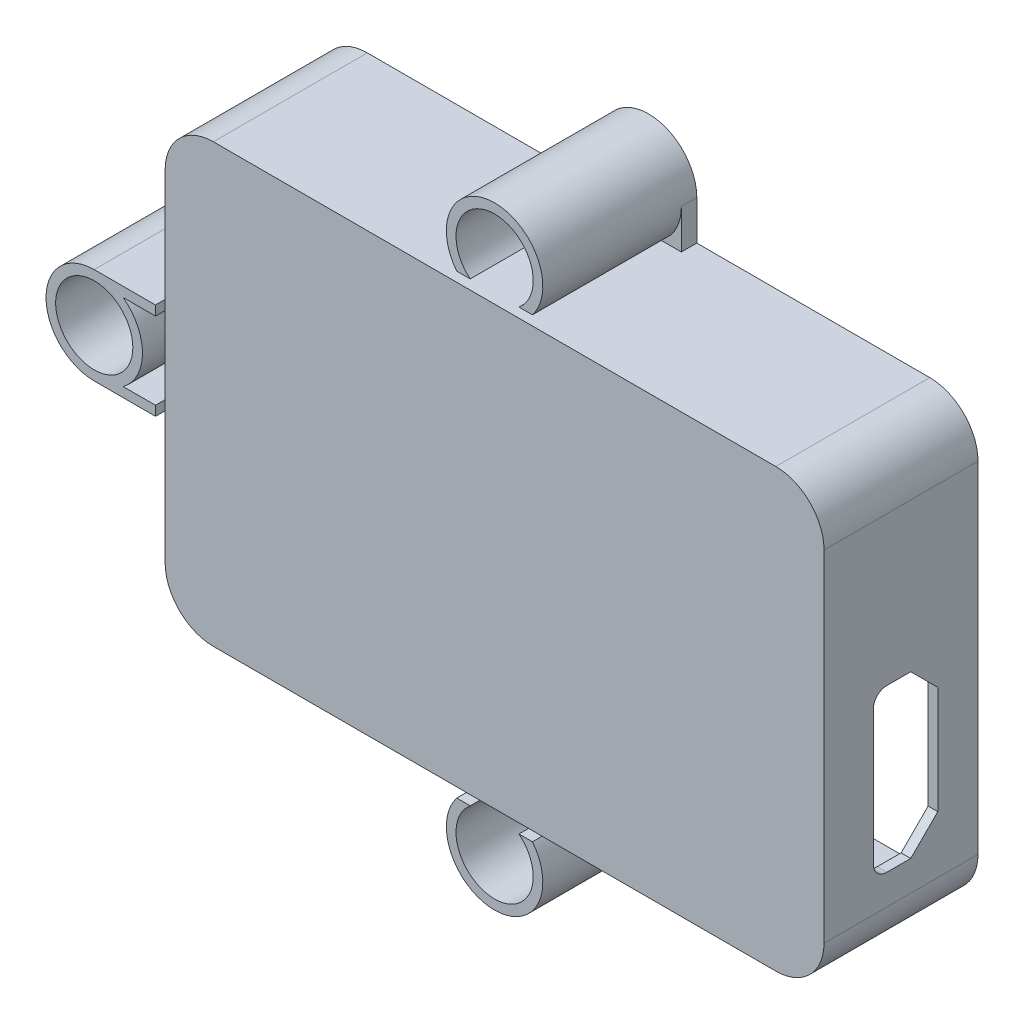
SolidWorks part; units mm, degrees
ref_plane "Front Plane" through (0, 0, 0) normal (0, 0, 1) x (1, 0, 0)
ref_plane "Top Plane" through (0, 0, 0) normal (0, 1, 0) x (1, 0, 0)
ref_plane "Right Plane" through (0, 0, 0) normal (1, 0, 0) x (0, 0, -1)
sketch "Sketch1" plane through (0, 0, 0) normal (0, 0, 1) x (1, 0, 0)
  line L1 (-14.575, -11.325) -> (14.575, -11.325)
  line L2 (-17.075, -8.825) -> (-17.075, 8.825)
  line L3 (-14.575, 11.325) -> (14.575, 11.325)
  line L4 (17.075, -8.825) -> (17.075, 8.825)
  line L5 (-17.075, -11.325) -> (17.075, 11.325) construction
  line L6 (-17.075, 11.325) -> (17.075, -11.325) construction
  line L8 (-16.575, 10.825) -> (-17.075, 10.825) construction
  line L9 (14.575, -10.825) -> (-14.575, -10.825)
  line L10 (16.575, -8.825) -> (16.575, 8.825)
  line L11 (14.575, 10.825) -> (-14.575, 10.825)
  line L12 (-16.575, -8.825) -> (-16.575, 8.825)
  line L13 (16.575, -10.825) -> (-16.575, 10.825) construction
  line L14 (16.575, 10.825) -> (-16.575, -10.825) construction
  line L15 (-16.575, 10.825) -> (-16.575, 11.325) construction
  line L16 (-16.375, 9.825) -> (-16.375, -9.825) construction
  line L17 (16.375, 9.825) -> (-16.375, 9.825) construction
  line L18 (-2.5, 13.375) -> (-2.5, 11.325)
  line L19 (2.5, 13.375) -> (2.5, 11.325)
  line L20 (-2.5, -13.375) -> (-2.5, -11.325)
  line L21 (2.5, -13.375) -> (2.5, -11.325)
  line L22 (-20.75, 2.5) -> (-17.075, 2.5)
  line L23 (-20.75, -2.5) -> (-17.075, -2.5)
  arc A0 (-14.575, -10.825) -> (-16.575, -8.825) centre (-14.575, -8.825) cw
  arc A1 (-2.4744, -13.0179) -> (2.4744, -13.0179) centre (0, -13.375) ccw construction
  arc A2 (14.575, -10.825) -> (16.575, -8.825) centre (14.575, -8.825) ccw
  arc A3 (16.575, 8.825) -> (14.575, 10.825) centre (14.575, 8.825) ccw
  arc A4 (-20.3929, 2.4744) -> (-20.3929, -2.4744) centre (-20.75, 0) ccw construction
  arc A5 (-14.575, 10.825) -> (-16.575, 8.825) centre (-14.575, 8.825) ccw
  arc A6 (-14.575, -11.325) -> (-17.075, -8.825) centre (-14.575, -8.825) cw
  arc A7 (14.575, -11.325) -> (17.075, -8.825) centre (14.575, -8.825) ccw
  arc A8 (2.4744, 13.0179) -> (-2.4744, 13.0179) centre (0, 13.375) ccw construction
  circle A9 centre (-20.75, 0) radius 1.25
  arc A10 (-2.4744, -13.0179) -> (2.4744, -13.0179) centre (0, -13.375) ccw
  circle A11 centre (0, 13.375) radius 1.25
  circle A12 centre (0, -13.375) radius 1.25
  arc A13 (-20.3929, 2.4744) -> (-20.3929, -2.4744) centre (-20.75, 0) ccw
  arc A14 (14.575, 11.325) -> (17.075, 8.825) centre (14.575, 8.825) cw
  arc A15 (-17.075, 8.825) -> (-14.575, 11.325) centre (-14.575, 8.825) cw
  arc A17 (2.4744, 13.0179) -> (-2.4744, 13.0179) centre (0, 13.375) ccw
  point P0 (0, 0)
  point P31 (0, 0)
  dimension "D4" = 2.5
  dimension "D5" = 2
  dimension "D6" = 2.5
  dimension "D1" = 0.5
  dimension "D2" = 0.2
  dimension "D3" = 1
extrude "Boss-Extrude1" add sketch "Sketch1" along normal offset from surface (7.48 mm away) 2.5 contours A13 L2 | L1 L4 L3 L2 L9 L12 L11 L10 | A17 L3 | A10 L1 region at (-16.053, -10.303, 0) region at (0, -11.3926, 0) region at (-18.9125, -2.4205, 0) region at (-2.4324, 12.35, 0) offset beyond the face yes
sketch "Sketch2" plane through (0, 0, 7.48) normal (0, 0, 1) x (1, 0, 0)
  line L0 (-2.5, 11.325) -> (2.5, 11.325)
  line L1 (-17.075, 2.5) -> (-17.075, -2.5)
  line L2 (-2.5, -11.325) -> (2.5, -11.325)
  line L13 (-17.075, 2.5) -> (-20.75, 2.5)
  line L14 (-20.75, -2.5) -> (-17.075, -2.5)
  line L15 (-17.075, -2.5) -> (-17.075, -8.825)
  line L16 (-14.575, -11.325) -> (-2.5, -11.325)
  line L17 (-2.5, -11.325) -> (-2.5, -13.375)
  line L18 (2.5, -13.375) -> (2.5, -11.325)
  line L19 (2.5, -11.325) -> (14.575, -11.325)
  line L20 (17.075, -8.825) -> (17.075, 8.825)
  line L21 (14.575, 11.325) -> (2.5, 11.325)
  line L22 (2.5, 11.325) -> (2.5, 13.375)
  line L23 (-2.5, 13.375) -> (-2.5, 11.325)
  line L24 (-2.5, 11.325) -> (-14.575, 11.325)
  line L25 (-17.075, 8.825) -> (-17.075, 2.5)
  line L26 (-17.075, 2.5) -> (-20.75, 2.5)
  line L27 (-20.75, -2.5) -> (-17.075, -2.5)
  line L28 (-17.075, -2.5) -> (-17.075, -8.825)
  line L29 (-14.575, -11.325) -> (-2.5, -11.325)
  line L30 (-2.5, -11.325) -> (-2.5, -13.375)
  line L31 (2.5, -13.375) -> (2.5, -11.325)
  line L32 (2.5, -11.325) -> (14.575, -11.325)
  line L33 (17.075, -8.825) -> (17.075, 8.825)
  line L34 (14.575, 11.325) -> (2.5, 11.325)
  line L35 (2.5, 11.325) -> (2.5, 13.375)
  line L36 (-2.5, 13.375) -> (-2.5, 11.325)
  line L37 (-2.5, 11.325) -> (-14.575, 11.325)
  line L38 (-17.075, 8.825) -> (-17.075, 2.5)
  arc A7 (-20.75, 2.5) -> (-20.75, -2.5) centre (-20.75, 0) ccw
  arc A8 (-17.075, -8.825) -> (-14.575, -11.325) centre (-14.575, -8.825) ccw
  arc A9 (-2.5, -13.375) -> (2.5, -13.375) centre (0, -13.375) ccw
  arc A10 (14.575, -11.325) -> (17.075, -8.825) centre (14.575, -8.825) ccw
  arc A11 (17.075, 8.825) -> (14.575, 11.325) centre (14.575, 8.825) ccw
  arc A12 (2.5, 13.375) -> (-2.5, 13.375) centre (0, 13.375) ccw
  arc A13 (-14.575, 11.325) -> (-17.075, 8.825) centre (-14.575, 8.825) ccw
  arc A14 (-20.75, 2.5) -> (-20.75, -2.5) centre (-20.75, 0) ccw
  arc A15 (-17.075, -8.825) -> (-14.575, -11.325) centre (-14.575, -8.825) ccw
  arc A16 (-2.5, -13.375) -> (2.5, -13.375) centre (0, -13.375) ccw
  arc A17 (14.575, -11.325) -> (17.075, -8.825) centre (14.575, -8.825) ccw
  arc A18 (17.075, 8.825) -> (14.575, 11.325) centre (14.575, 8.825) ccw
  arc A19 (2.5, 13.375) -> (-2.5, 13.375) centre (0, 13.375) ccw
  arc A20 (-14.575, 11.325) -> (-17.075, 8.825) centre (-14.575, 8.825) ccw
  dimension "D1" = 0
extrude "Cut-Extrude1" cut sketch "Sketch2" against normal offset from surface (6.68 mm away) 0.8 contours L0 | L1 | L2 region at (0, 13.3705, 7.48) region at (-19.9219, 0, 7.48) region at (0, -13.3705, 7.48) up to face at (-3.9075, 0, 0)
sketch "Sketch3" plane through (17.075, 0, 0) normal (1, 0, 0) x (0, 0, -1)
  line L0 (-3.98, -7.065) -> (-4.18, -7.065) construction
  line L1 (-5.425, -7.265) -> (-2.085, -7.265)
  line L2 (-5.425, -7.265) -> (-5.425, 1.115)
  line L3 (-5.425, 1.115) -> (-2.085, 1.115)
  line L4 (-2.085, -7.265) -> (-2.085, 1.115)
  line L5 (-5.225, -6.075) -> (-5.425, -6.075) construction
  line L6 (-4.18, -7.065) -> (-4.18, -7.265) construction
  line L7 (-4.18, 0.915) -> (-4.18, 1.115) construction
  line L8 (-2.285, -5.375) -> (-2.085, -5.375) construction
  dimension "D1" = 0.2
extrude "Cut-Extrude2" cut sketch "Sketch3" against normal up to next
chamfer "Chamfer1" distance 1.4 angle 45 2 edges at (16.825, 1.115, 2.085) (16.825, -7.265, 2.085)
fillet "Fillet1" radius 0.7 2 edges at (16.825, 1.115, 5.425) (16.825, -7.265, 5.425)
sketch "Sketch4" plane through (0, 0, 7.48) normal (0, 0, 1) x (1, 0, 0)
  line L4 (-17.075, 8.825) -> (-17.075, -8.825)
  line L5 (-14.575, -11.325) -> (14.575, -11.325)
  line L6 (17.075, -8.825) -> (17.075, 8.825)
  line L7 (14.575, 11.325) -> (-14.575, 11.325)
  line L8 (-17.075, 8.825) -> (-17.075, -8.825)
  line L9 (-14.575, -11.325) -> (14.575, -11.325)
  line L10 (17.075, -8.825) -> (17.075, 8.825)
  line L11 (14.575, 11.325) -> (-14.575, 11.325)
  arc A4 (-17.075, -8.825) -> (-14.575, -11.325) centre (-14.575, -8.825) ccw
  arc A5 (14.575, -11.325) -> (17.075, -8.825) centre (14.575, -8.825) ccw
  arc A6 (17.075, 8.825) -> (14.575, 11.325) centre (14.575, 8.825) ccw
  arc A7 (-14.575, 11.325) -> (-17.075, 8.825) centre (-14.575, 8.825) ccw
  arc A8 (-17.075, -8.825) -> (-14.575, -11.325) centre (-14.575, -8.825) ccw
  arc A9 (14.575, -11.325) -> (17.075, -8.825) centre (14.575, -8.825) ccw
  arc A10 (17.075, 8.825) -> (14.575, 11.325) centre (14.575, 8.825) ccw
  arc A11 (-14.575, 11.325) -> (-17.075, 8.825) centre (-14.575, 8.825) ccw
  dimension "D1" = 0
extrude "Boss-Extrude2" add sketch "Sketch4" along normal blind 0.5
sketch "Sketch6" plane through (0, 0, 7.48) normal (0, 0, -1) x (-1, 0, 0)
  line L1 (-14.575, -10.825) -> (-16.575, -10.825)
  line L2 (-14.575, -10.825) -> (-14.575, -9.325)
  line L3 (-14.575, -9.325) -> (-16.575, -9.325)
  line L4 (16.575, -8.825) -> (16.575, 8.825)
  line L5 (14.575, 10.825) -> (-14.575, 10.825)
  line L6 (-16.575, 8.825) -> (-16.575, -8.825)
  line L7 (-14.575, -10.825) -> (14.575, -10.825)
  line L8 (16.575, -8.825) -> (16.575, 8.825)
  line L9 (14.575, 10.825) -> (-14.575, 10.825)
  line L10 (-16.575, 8.825) -> (-16.575, -8.825)
  line L11 (-14.575, -10.825) -> (14.575, -10.825)
  line L12 (-16.575, -10.825) -> (-16.575, -9.325)
  line L13 (-16.575, 1.915) -> (-14.575, 1.915)
  line L14 (-16.575, 1.915) -> (-16.575, 3.415)
  line L15 (-16.575, 3.415) -> (-14.575, 3.415)
  line L16 (-14.575, 1.915) -> (-14.575, 3.415)
  line L17 (-14.575, 10.825) -> (-16.575, 10.825)
  line L18 (-14.575, 10.825) -> (-14.575, 9.325)
  line L19 (-14.575, 9.325) -> (-16.575, 9.325)
  line L20 (-16.575, 10.825) -> (-16.575, 9.325)
  line L21 (16.575, 10.825) -> (14.575, 10.825)
  line L22 (16.575, 10.825) -> (16.575, 9.325)
  line L23 (16.575, 9.325) -> (14.575, 9.325)
  line L24 (14.575, 10.825) -> (14.575, 9.325)
  line L25 (10.575, -10.825) -> (7.575, -10.825)
  line L26 (10.575, -10.825) -> (10.575, -9.325)
  line L27 (10.575, -9.325) -> (7.575, -9.325)
  line L28 (7.575, -10.825) -> (7.575, -9.325)
  arc A4 (14.575, -10.825) -> (16.575, -8.825) centre (14.575, -8.825) ccw
  arc A5 (16.575, 8.825) -> (14.575, 10.825) centre (14.575, 8.825) ccw
  arc A6 (-14.575, 10.825) -> (-16.575, 8.825) centre (-14.575, 8.825) ccw
  arc A7 (-16.575, -8.825) -> (-14.575, -10.825) centre (-14.575, -8.825) ccw
  arc A8 (14.575, -10.825) -> (16.575, -8.825) centre (14.575, -8.825) ccw
  arc A9 (16.575, 8.825) -> (14.575, 10.825) centre (14.575, 8.825) ccw
  arc A10 (-14.575, 10.825) -> (-16.575, 8.825) centre (-14.575, 8.825) ccw
  arc A11 (-16.575, -8.825) -> (-14.575, -10.825) centre (-14.575, -8.825) ccw
  dimension "D2" = 1.5
  dimension "D3" = 1.5
  dimension "D5" = 3
  dimension "D6" = 6
  dimension "D1" = 0
extrude "Boss-Extrude4" add sketch "Sketch6" along normal offset from surface (4.98 mm away) 2.5 contours L28 L11 L26 L27 | L2 L3 | L13 L16 L15 L10 | L19 L18 | L24 L23 region at (15.3591, -9.9498, 7.48) region at (-9.075, -10.075, 7.48) region at (15.575, 2.665, 7.48) region at (-15.3591, 9.9498, 7.48) region at (15.3591, 9.9498, 7.48) up to face at (-3.9075, 0, 0)
sketch "Sketch7" plane through (0, 0, 7.48) normal (0, 0, -1) x (-1, 0, 0)
  line L0 (16.575, -8.825) -> (16.575, 8.825) construction
  line L1 (16.575, 4.185) -> (10.455, 4.185)
  line L2 (16.575, 4.185) -> (16.575, 6.185)
  line L3 (16.575, 6.185) -> (10.455, 6.185)
  line L4 (10.455, 4.185) -> (10.455, 6.185)
  line L5 (16.875, 3.985) -> (10.655, 3.985) construction
  line L6 (10.655, 3.985) -> (10.655, 4.185) construction
  line L7 (10.455, 2.5) -> (5.855, 2.5)
  line L8 (10.455, 2.5) -> (10.455, 4.5)
  line L9 (10.455, 4.5) -> (5.855, 4.5)
  line L10 (5.855, 2.5) -> (5.855, 4.5)
  line L11 (10.655, 3.985) -> (10.455, 3.985) construction
  line L12 (10.455, 2.5) -> (10.455, 2.3) construction
  line L13 (10.655, 2.3) -> (6.055, 2.3) construction
  line L14 (6.055, 2.3) -> (5.855, 2.3) construction
  line L15 (5.855, 3.8) -> (3.855, 3.8)
  line L16 (5.855, 3.8) -> (5.855, 1.8)
  line L17 (5.855, 1.8) -> (3.855, 1.8)
  line L18 (3.855, 3.8) -> (3.855, 1.8)
  line L19 (-5.1149, 0) -> (3.3954, 0) construction
  line L20 (16.575, -4.185) -> (16.575, -6.185)
  line L21 (16.575, -6.185) -> (10.455, -6.185)
  line L22 (16.575, -4.185) -> (10.455, -4.185)
  line L23 (10.455, -4.185) -> (10.455, -6.185)
  line L24 (10.455, -2.5) -> (10.455, -4.5)
  line L25 (10.455, -4.5) -> (5.855, -4.5)
  line L26 (5.855, -2.5) -> (5.855, -4.5)
  line L27 (10.455, -2.5) -> (5.855, -2.5)
  line L28 (5.855, -3.8) -> (5.855, -1.8)
  line L29 (5.855, -3.8) -> (3.855, -3.8)
  line L30 (3.855, -3.8) -> (3.855, -1.8)
  line L31 (5.855, -1.8) -> (3.855, -1.8)
  line M32 (16.575, -8.825) -> (16.575, 8.825)
  dimension "D1" = 0.2
  dimension "D2" = 2
  dimension "D3" = 0.5
extrude "Boss-Extrude5" add sketch "Sketch7" along normal blind 2.5 contours L4 L1 L3 M32 | L10 L7 L8 L4 L9 | L15 L18 L17 L16 L10 | L28 L31 L30 L29 L26 | L24 L27 L26 L25 L23 | L22 L23 L21 M32 region at (-13.515, 5.185, 7.48) region at (-13.515, -5.185, 7.48) region at (-8.155, 3.5, 7.48) region at (-8.155, -3.5, 7.48) region at (-4.855, 2.8, 7.48) region at (-4.855, -2.8, 7.48)
sketch "Sketch8" plane through (-17.075, 0, 0) normal (-1, 0, 0) x (0, 0, 1)
  line L0 (7.48, -4.185) -> (7.48, 4.185) construction
  line L1 (7.48, -4.185) -> (4.88, -4.185)
  line L2 (7.48, -4.185) -> (7.48, 4.185)
  line L3 (7.48, 4.185) -> (4.88, 4.185)
  line L4 (4.88, -4.185) -> (4.88, 4.185)
  line L5 (4.98, 4.185) -> (7.48, 4.185) construction
  line L6 (4.98, -4.185) -> (7.48, -4.185) construction
  dimension "D1" = 2.6
extrude "Cut-Extrude3" cut sketch "Sketch8" against normal up to next
sketch "Sketch5" plane through (0, 0, 0.8) normal (0, 0, 1) x (1, 0, 0)
  line L0 (2.5, -13.375) -> (2.5, -11.325) construction
  line L1 (2.5, -11.325) -> (-2.5, -11.325) construction
  line L2 (-2.5, -11.325) -> (-2.5, -13.375) construction
  line L3 (-2.5, 13.375) -> (-2.5, 11.325) construction
  line L4 (-2.5, 11.325) -> (2.5, 11.325) construction
  line L5 (2.5, 11.325) -> (2.5, 13.375) construction
  line L6 (-20.75, -2.5) -> (-17.075, -2.5) construction
  line L7 (-17.075, -2.5) -> (-17.075, 2.5) construction
  line L8 (-17.075, 2.5) -> (-20.75, 2.5) construction
  line L9 (2.5, -13.375) -> (2.5, -11.325)
  line L10 (2.5, -11.325) -> (-2.5, -11.325)
  line L11 (-2.5, -11.325) -> (-2.5, -13.375)
  line L12 (-2.5, 13.375) -> (-2.5, 11.325)
  line L13 (-2.5, 11.325) -> (2.5, 11.325)
  line L14 (2.5, 11.325) -> (2.5, 13.375)
  line L15 (-20.75, -2.5) -> (-17.075, -2.5)
  line L16 (-17.075, -2.5) -> (-17.075, 2.5)
  line L17 (-17.075, 2.5) -> (-20.75, 2.5)
  line L18 (-2.5, 11.825) -> (2.5, 11.825)
  line L19 (-20.75, 2) -> (-20.75, 2.5) construction
  line L20 (0, 11.825) -> (0, 11.325) construction
  line L21 (-17.075, 0) -> (17.075, 0) construction
  line L22 (17.075, -8.825) -> (17.075, 8.825) construction
  line L23 (-2.5, -11.825) -> (2.5, -11.825)
  line L24 (-17.575, 2.25) -> (-17.075, 2.25) construction
  line L25 (-20.75, 2.5) -> (-17.575, 2.5)
  line L26 (-20.75, 2.5) -> (-20.75, 2)
  line L27 (-20.75, 2) -> (-17.575, 2)
  line L28 (-17.575, 2.5) -> (-17.575, 2)
  line L29 (-20.75, -2.5) -> (-20.75, -2)
  line L30 (-20.75, -2) -> (-17.575, -2)
  line L31 (-17.575, -2.5) -> (-17.575, -2)
  line L32 (-17.075, -2.5) -> (-20.75, -2.5)
  arc A0 (-2.5, -13.375) -> (2.5, -13.375) centre (0, -13.375) ccw construction
  arc A1 (2.5, 13.375) -> (-2.5, 13.375) centre (0, 13.375) ccw construction
  arc A2 (-20.75, 2.5) -> (-20.75, -2.5) centre (-20.75, 0) ccw construction
  arc A3 (-2.5, -13.375) -> (2.5, -13.375) centre (0, -13.375) ccw
  arc A4 (2.5, 13.375) -> (-2.5, 13.375) centre (0, 13.375) ccw
  arc A5 (-20.75, 2.5) -> (-20.75, -2.5) centre (-20.75, 0) ccw
  circle A6 centre (-20.75, 0) radius 2
  circle A7 centre (-20.75, 0) radius 2.5
  circle A8 centre (0, 13.375) radius 2.5
  circle A9 centre (0, -13.375) radius 2.5
  circle A10 centre (0, 13.375) radius 2
  circle A11 centre (0, -13.375) radius 2
  line M6 (-20.75, -2.5) -> (-17.075, -2.5)
  arc M9 (-20.75, 2.5) -> (-20.75, -2.5) centre (-20.75, 0) ccw
  dimension "D1" = 0.5
extrude "Boss-Extrude3" add sketch "Sketch5" along normal up to surface (7.18 mm away) contours A10 L18 A8 A4 | A7 A6 M9 | A11 L23 A9 A3 | L30 A7 L27 A6 | L27 A7 L26 | A7 L27 L28 L17 | A7 L31 L30 M6 | L29 A7 L30 region at (0, -15.8107, 0.8) region at (0, 15.8107, 0.8) region at (-18.68, -2.2729, 0.8) region at (-23.1941, 0, 0.8) region at (-20.1792, -2.2018, 0.8) region at (-19.3024, -1.4476, 0.8) region at (-20.1792, 2.2018, 0.8) region at (-18.68, 2.2729, 0.8) up to face at (0, 0, 7.98)
